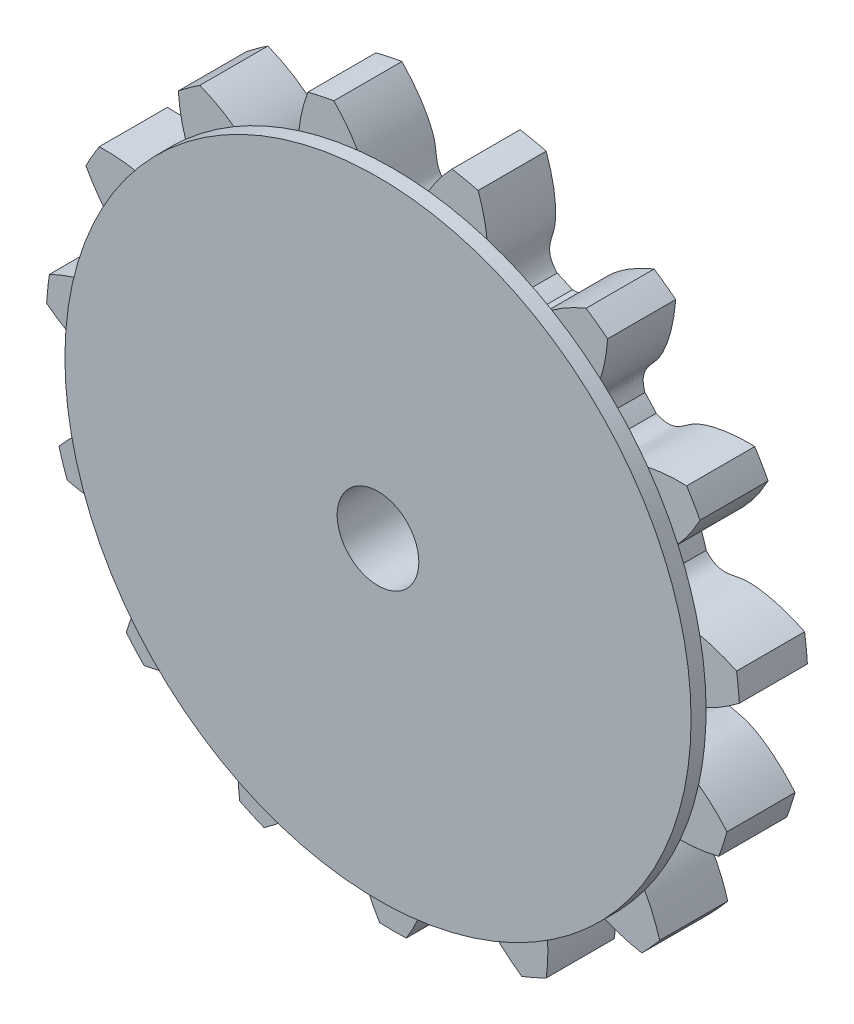
SolidWorks part; units mm, degrees
ref_plane "前视基准面" through (0, 0, 0) normal (0, 0, 1) x (1, 0, 0)
ref_plane "上视基准面" through (0, 0, 0) normal (0, 1, 0) x (1, 0, 0)
ref_plane "右视基准面" through (0, 0, 0) normal (1, 0, 0) x (0, 0, -1)
sketch "草图1" plane through (0, 0, 0) normal (0, 0, 1) x (1, 0, 0)
  circle A0 centre (0, 0) radius 5.1
extrude "凸台-拉伸1" add sketch "草图1" along normal blind 1
ref_axis "基准轴1" through (0, 0, -1.5) along (0, 0, 1)
sketch "草图2" plane through (0, 0, 0) normal (0, 0, 1) x (1, 0, 0)
  line L0 (0, 0) -> (0, 5.1) construction
  circle A0 centre (0, 0) radius 5.1 construction
  arc A1 (0.1226, 3.748) -> (-0.1226, 3.748) centre (0, 0) ccw
  arc A2 (1.9481, 5.7816) -> (-1.9481, 5.7816) centre (0, 0) ccw
  spline S0 degree 3 poles (0.1226, 3.748) (0.3943, 3.8606) (0.3433, 4.0718) (0.3908, 4.2651) (0.3945, 4.279) (0.3989, 4.2944) (0.4042, 4.3114) (0.4103, 4.3299) (0.4174, 4.3498) (0.4254, 4.3712) (0.4345, 4.3939) (0.4447, 4.4181) (0.4561, 4.4436) (0.4687, 4.4703) (0.4826, 4.4984) (0.4979, 4.5276) (0.5145, 4.5581) (0.5326, 4.5896) (0.5522, 4.6223) (0.5733, 4.6559) (0.596, 4.6906) (0.6204, 4.7262) (0.6464, 4.7627) (0.6742, 4.8) (0.7038, 4.838) (0.7352, 4.8768) (0.7684, 4.9163) (0.8035, 4.9564) (0.8406, 4.9969) (0.8797, 5.038) (0.9207, 5.0795) (0.9638, 5.1213) (1.0089, 5.1634) (1.0562, 5.2058) (1.1055, 5.2483) (1.157, 5.2908) (1.2107, 5.3334) (1.2666, 5.3759) (1.3246, 5.4183) (1.3849, 5.4605) (1.4474, 5.5024) (1.5122, 5.544) (1.5792, 5.5852) (1.6485, 5.6258) (1.7201, 5.6659) (1.8196, 5.7191) (1.8961, 5.757) (1.9481, 5.7816) knots 0 0 0 0 0.202473 0.206979 0.212085 0.217793 0.224101 0.23101 0.23852 0.24663 0.255341 0.264653 0.274566 0.285079 0.296194 0.307909 0.320225 0.333141 0.346659 0.360777 0.375496 0.390816 0.406736 0.423257 0.440379 0.458102 0.476426 0.49535 0.514875 0.535001 0.555728 0.577055 0.598984 0.621513 0.644642 0.668373 0.692704 0.717636 0.743169 0.769303 0.796037 0.823373 0.851309 0.879845 0.908983 0.938721 1 1 1 1
  spline S1 degree 3 poles (-0.1226, 3.748) (-0.3943, 3.8606) (-0.3433, 4.0718) (-0.3908, 4.2651) (-0.3945, 4.279) (-0.3989, 4.2944) (-0.4042, 4.3114) (-0.4103, 4.3299) (-0.4174, 4.3498) (-0.4254, 4.3712) (-0.4345, 4.3939) (-0.4447, 4.4181) (-0.4561, 4.4436) (-0.4687, 4.4703) (-0.4826, 4.4984) (-0.4979, 4.5276) (-0.5145, 4.5581) (-0.5326, 4.5896) (-0.5522, 4.6223) (-0.5733, 4.6559) (-0.596, 4.6906) (-0.6204, 4.7262) (-0.6464, 4.7627) (-0.6742, 4.8) (-0.7038, 4.838) (-0.7352, 4.8768) (-0.7684, 4.9163) (-0.8035, 4.9564) (-0.8406, 4.9969) (-0.8797, 5.038) (-0.9207, 5.0795) (-0.9638, 5.1213) (-1.0089, 5.1634) (-1.0562, 5.2058) (-1.1055, 5.2483) (-1.157, 5.2908) (-1.2107, 5.3334) (-1.2666, 5.3759) (-1.3246, 5.4183) (-1.3849, 5.4605) (-1.4474, 5.5024) (-1.5122, 5.544) (-1.5792, 5.5852) (-1.6485, 5.6258) (-1.7201, 5.6659) (-1.8196, 5.7191) (-1.8961, 5.757) (-1.9481, 5.7816) knots 0 0 0 0 0.202473 0.206979 0.212085 0.217793 0.224101 0.23101 0.23852 0.24663 0.255341 0.264653 0.274566 0.285079 0.296194 0.307909 0.320225 0.333141 0.346659 0.360777 0.375496 0.390816 0.406736 0.423257 0.440379 0.458102 0.476426 0.49535 0.514875 0.535001 0.555728 0.577055 0.598984 0.621513 0.644642 0.668373 0.692704 0.717636 0.743169 0.769303 0.796037 0.823373 0.851309 0.879845 0.908983 0.938721 1 1 1 1
extrude "切除-拉伸1" cut sketch "草图2" along normal through all
pattern_circular "阵列(圆周)1" count 15 every 24 about axis through (0, 0, -1.5) along (0, 0, 1) of "切除-拉伸1"
sketch "草图3" plane through (0, 0, 0) normal (0, 0, 1) x (1, 0, 0)
  circle A0 centre (0, 0) radius 4.5 construction
  dimension "Dn" = 9
sketch "草图5" plane through (0, 0, 1) normal (0, 0, 1) x (1, 0, 0)
  circle A0 centre (0, 0) radius 4.6
  dimension "D1" = 9.2
extrude "凸台-拉伸2" add sketch "草图5" along normal blind 0.22
sketch "草图4" plane through (0, 0, 1) normal (0, 0, 1) x (1, 0, 0)
  circle A0 centre (0, 0) radius 0.6
  dimension "D1" = 1.2
extrude "切除-拉伸2" cut sketch "草图4" against normal through all both and the other way through all
